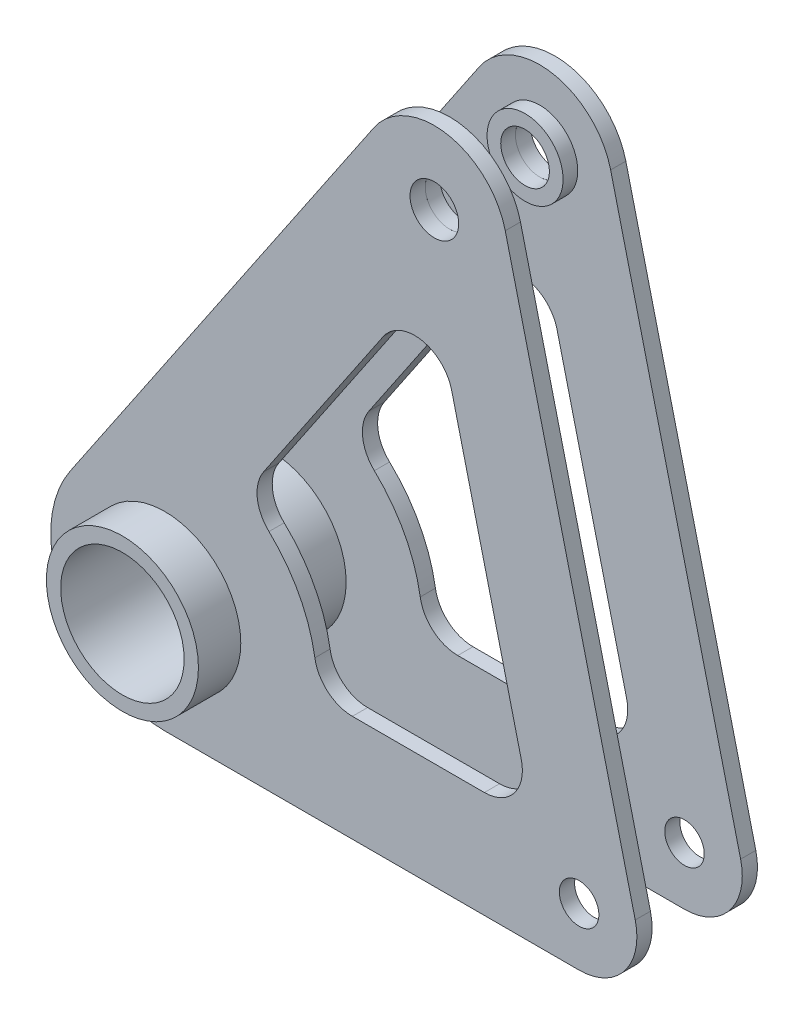
SolidWorks part; units mm, degrees
material "AISI 4130 Steel, normalized at 870C"
ref_plane "Front Plane" through (0, 0, 0) normal (0, 0, 1) x (1, 0, 0)
ref_plane "Top Plane" through (0, 0, 0) normal (0, 1, 0) x (1, 0, 0)
ref_plane "Right Plane" through (0, 0, 0) normal (1, 0, 0) x (0, 0, -1)
sketch "Sketch3" plane through (0, 0, 0) normal (0, 0, 1) x (1, 0, 0)
  circle A0 centre (0, 0) radius 9.525
  circle A1 centre (0, 0) radius 12.7
  dimension "D1" = 25.4
  dimension "D2" = 19.05
extrude "Bearing Back Stop" add sketch "Sketch3" along normal blind 1.27 and the other way blind 1.27
sketch "Sketch1" plane through (0, 0, 0) normal (0, 0, 1) x (1, 0, 0)
  circle A0 centre (0, 0) radius 10.3124
  circle A1 centre (0, 0) radius 12.7
  circle A2 centre (0, 0) radius 12.7 construction
  dimension "D2" = 20.6248
extrude "Bearing Mount" add sketch "Sketch1" along normal blind 17.145 and the other way blind 17.145
sketch "Sketch4" plane through (0, 0, 0) normal (0, 0, 1) x (1, 0, 0)
  line L0 (-15.7813, 10.6702) -> (34.9346, 85.6796)
  line L1 (0, -19.05) -> (69.2149, -19.05)
  line L2 (45.0346, 78.8507) -> (0, 0) construction
  line L3 (0, 0) -> (69.2149, -9.398) construction
  line L4 (13.97, 0) -> (-13.97, 0) construction
  line L5 (56.8781, 81.7449) -> (78.591, -7.1067)
  line L6 (69.2149, -9.398) -> (90.7627, 58.1678) construction
  line L7 (45.0346, 78.8507) -> (-16.7619, 121.5661) construction
  line L8 (45.0346, 78.8507) -> (69.2149, -9.398) construction
  line L10 (53.3876, -1.27) -> (31.341, -1.27)
  line L12 (47.9227, 54.1927) -> (59.5561, 6.5874)
  line L15 (16.5024, 26.6747) -> (36.4937, 56.2421)
  arc A0 (0, -19.05) -> (-15.7813, 10.6702) centre (0, 0) cw
  circle A1 centre (45.0346, 78.8507) radius 4.064
  circle A2 centre (69.2149, -9.398) radius 3.302
  arc A3 (34.9346, 85.6796) -> (56.8781, 81.7449) centre (45.0346, 78.8507) cw
  arc A4 (69.2149, -19.05) -> (78.591, -7.1067) centre (69.2149, -9.398) ccw
  circle A5 centre (0, 0) radius 12.7 construction
  circle A6 centre (0, 0) radius 12.7
  arc A7 (17.4103, 18.4944) -> (25.0728, 4.064) centre (0, 0) cw
  arc A8 (31.341, -1.27) -> (25.0728, 4.064) centre (31.341, 5.08) cw
  arc A9 (17.4103, 18.4944) -> (16.5024, 26.6747) centre (21.7629, 23.118) cw
  arc A10 (59.5561, 6.5874) -> (53.3876, -1.27) centre (53.3876, 5.08) cw
  arc A11 (47.9227, 54.1927) -> (36.4937, 56.2421) centre (41.7542, 52.6853) ccw
  dimension "D4" = 6.35
  dimension "D5" = 6.35
  dimension "D6" = 8.128
  dimension "D7" = 8.128
  dimension "D8" = 6.604
  dimension "D11" = 12.7
  dimension "D12" = 17.78
  dimension "D13" = 17.78
  dimension "D15" = 6.35
  dimension "D1" = 69.85
  dimension "D2" = 90.805
  dimension "D3" = 68
  dimension "D9" = 99.956
  dimension "D10" = 94.921
  dimension "D14" = 15.24
  dimension "D16" = 17.78
  dimension "D17" = 17.78
extrude "Bellcrank Plate" add sketch "Sketch4" along normal blind 2.54 from offset 7.5311 separate body
sketch "Sketch5" plane through (0, 0, 7.5311) normal (0, 0, -1) x (-1, 0, 0)
  circle A0 centre (-45.0346, 78.8507) radius 6.35
  circle A1 centre (-45.0346, 78.8507) radius 4.064 construction
  circle A2 centre (-45.0346, 78.8507) radius 4.064
  dimension "D1" = 12.7
extrude "Damper Washer" add sketch "Sketch5" along normal blind 2.4511 separate body
mirror "Bellcrank Mirror" about plane through (0, 0, 0) normal (0, 0, 1) of bodies 103 105
